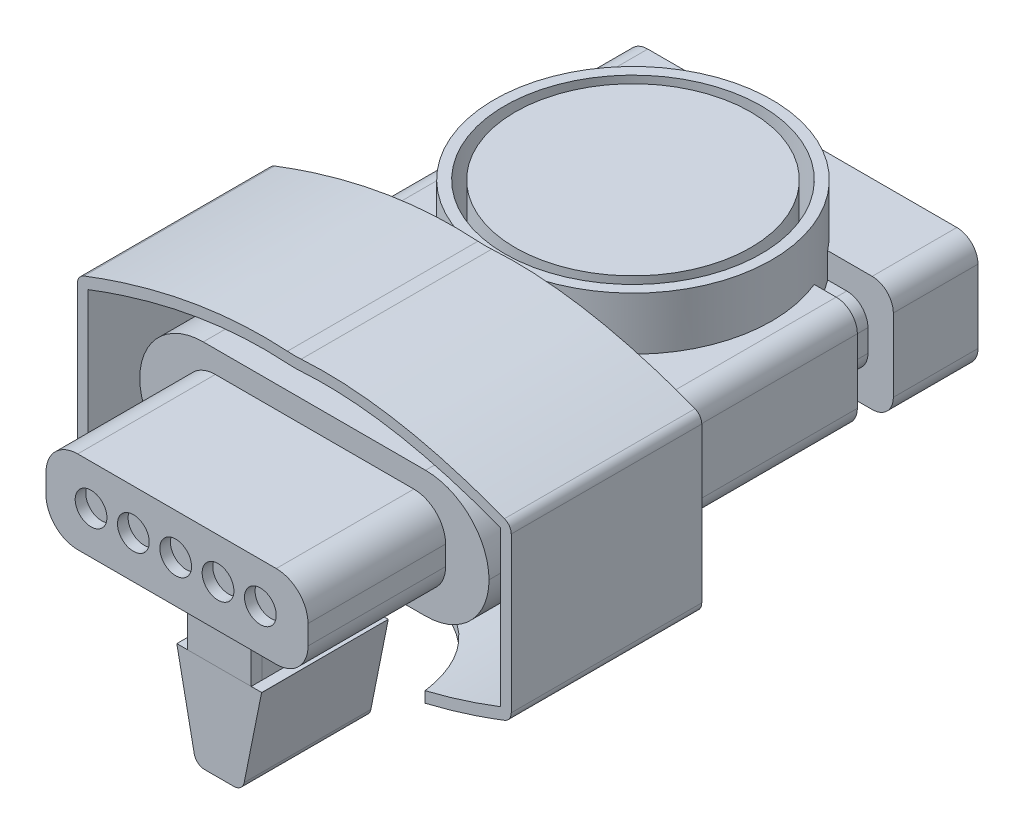
SolidWorks part; units mm, degrees
ref_plane "正面" through (0, 0, 0) normal (0, 0, 1) x (1, 0, 0)
ref_plane "平面" through (0, 0, 0) normal (0, 1, 0) x (1, 0, 0)
ref_plane "右側面" through (0, 0, 0) normal (1, 0, 0) x (0, 0, -1)
sketch "ｽｹｯﾁ1" plane through (0, 0, 0) normal (0, 0, 1) x (1, 0, 0)
  line L1 (0, 0) -> (33.2, 0)
  line L2 (0, 0) -> (0, 10.9)
  line L3 (0, 10.9) -> (33.2, 10.9)
  line L4 (33.2, 0) -> (33.2, 10.9)
  dimension "D1" = 10.9
  dimension "D2" = 33.2
extrude "ﾎﾞｽ - 押し出し1" add sketch "ｽｹｯﾁ1" along normal blind 8
sketch "ｽｹｯﾁ2" plane through (0, 0, 8) normal (0, 0, 1) x (1, 0, 0)
  line L8 (2.4, 8.5) -> (2.4, 2.4)
  line L9 (2.4, 2.4) -> (30.8, 2.4)
  line L10 (30.8, 2.4) -> (30.8, 8.5)
  line L11 (30.8, 8.5) -> (2.4, 8.5)
  line L12 (2.4, 8.5) -> (2.4, 2.4)
  line L13 (2.4, 2.4) -> (30.8, 2.4)
  line L14 (30.8, 2.4) -> (30.8, 8.5)
  line L15 (30.8, 8.5) -> (2.4, 8.5)
  dimension "D1" = 2.4
extrude "ﾎﾞｽ - 押し出し2" add sketch "ｽｹｯﾁ2" along normal blind 3
sketch "ｽｹｯﾁ3" plane through (0, 0, 11) normal (0, 0, 1) x (1, 0, 0)
  line L12 (32.8, 10.5) -> (0.4, 10.5)
  line L13 (0.4, 10.5) -> (0.4, 0.4)
  line L14 (0.4, 0.4) -> (32.8, 0.4)
  line L15 (32.8, 0.4) -> (32.8, 10.5)
  line L16 (32.8, 10.5) -> (0.4, 10.5)
  line L17 (0.4, 10.5) -> (0.4, 0.4)
  line L18 (0.4, 0.4) -> (32.8, 0.4)
  line L19 (32.8, 0.4) -> (32.8, 10.5)
  dimension "D1" = 2
extrude "ﾎﾞｽ - 押し出し3" add sketch "ｽｹｯﾁ3" along normal blind 19
sketch "ｽｹｯﾁ4" plane through (0, 0, 30) normal (0, 0, 1) x (1, 0, 0)
  line L1 (0.4, 10.5) -> (0.4, 0.4) construction
  line L2 (-3.9, -2.55) -> (-3.9, 13.45)
  line L3 (0.4, 5.45) -> (32.8, 5.45) construction
  line L4 (32.8, 0.4) -> (32.8, 10.5) construction
  line L5 (16.6, 10.5) -> (16.6, 0.4) construction
  line L6 (32.8, 10.5) -> (0.4, 10.5) construction
  line L7 (0.4, 0.4) -> (32.8, 0.4) construction
  line L8 (37.1, -2.55) -> (37.1, 13.45)
  line L9 (-3.9, 5.45) -> (-3.9, 13.45)
  spline S0 degree 3 poles (16.6, 17.1) (9.5929, 17.6967) (2.5741, 16.014) (-3.9, 13.45) knots 0 0 0 0 1 1 1 1
  spline S1 degree 3 poles (16.6, 17.1) (23.6071, 17.6967) (30.6259, 16.014) (37.1, 13.45) knots 0 0 0 0 1 1 1 1
  spline S2 degree 3 poles (16.6, -6.2) (23.6071, -6.7967) (30.6259, -5.114) (37.1, -2.55) knots 0 0 0 0 1 1 1 1
  spline S3 degree 3 poles (16.6, -6.2) (9.5929, -6.7967) (2.5741, -5.114) (-3.9, -2.55) knots 0 0 0 0 1 1 1 1
  point P22 (37.1, 5.45)
  dimension "D1" = 4.3
  dimension "D2" = 8
  dimension "D3" = 6.6
extrude "ﾎﾞｽ - 押し出し4" add sketch "ｽｹｯﾁ4" along normal blind 18 contours S0 S1 L8 S2 S3 L2
fillet "ﾌｨﾚｯﾄ1" radius 10 2 edges at (16.6, 17.1, 39) (16.6, -6.2, 39)
sketch "ｽｹｯﾁ5" plane through (0, 0, 48) normal (0, 0, 1) x (1, 0, 0)
  line L4 (-2.9, 12.7669) -> (-2.9, -1.8669)
  line L5 (36.1, -1.8669) -> (36.1, 12.7669)
  line L6 (-2.9, 12.7669) -> (-2.9, -1.8669)
  line L7 (36.1, -1.8669) -> (36.1, 12.7669)
  arc A4 (17.3158, -5.251) -> (15.8842, -5.251) centre (16.6, -16.2277) ccw
  arc A5 (15.8842, 16.151) -> (17.3158, 16.151) centre (16.6, 27.1277) ccw
  arc A6 (17.3158, -5.251) -> (15.8842, -5.251) centre (16.6, -16.2277) ccw
  arc A7 (15.8842, 16.151) -> (17.3158, 16.151) centre (16.6, 27.1277) ccw
  spline S8 degree 3 poles (-1595.7117, -3656.5086) (-104.425, 409.5804) (-109.7633, 29.6537) (3.1945, -3.8808) (4.7522, -4.2703) (7.1155, -4.729) (7.9088, -4.861) (9.4961, -5.0774) (10.291, -5.1621) (97.7123, -11.6496) (201.401, 283.2228) (496.6372, 3960.3055) knots -17.845867 -17.845867 -17.845867 -17.845867 0.25 0.25 0.5 0.5 0.625 0.625 0.75 0.75 14.346286 14.346286 14.346286 14.346286 only from (-2.9, -1.8669) to (15.8842, -5.251)
  spline S9 degree 3 poles (-303.7203, 3976.0592) (-161.6754, 304.9336) (-67.4702, -11.89) (22.9214, -5.161) (23.7203, -5.0755) (25.3086, -4.8583) (26.0992, -4.7264) (27.6736, -4.4203) (28.4581, -4.2459) (30.0141, -3.8604) (30.7864, -3.6491) (144.2827, 30.066) (147.6404, 421.65) (1528.8318, -3697.9846) knots -13.74633 -13.74633 -13.74633 -13.74633 0.25 0.25 0.375 0.375 0.5 0.5 0.625 0.625 0.75 0.75 19.116032 19.116032 19.116032 19.116032 only from (17.3158, -5.251) to (36.1, -1.8669)
  spline S10 degree 3 poles (1628.9117, 3667.4086) (137.625, -398.6804) (142.9633, -18.7537) (30.0055, 14.7808) (28.4478, 15.1703) (26.0845, 15.629) (25.2912, 15.761) (23.7039, 15.9774) (22.909, 16.0621) (-64.5123, 22.5496) (-168.201, -272.3228) (-463.4372, -3949.4055) knots -17.845867 -17.845867 -17.845867 -17.845867 0.25 0.25 0.5 0.5 0.625 0.625 0.75 0.75 14.346286 14.346286 14.346286 14.346286 only from (36.1, 12.7669) to (17.3158, 16.151)
  spline S11 degree 3 poles (336.9203, -3965.1592) (194.8754, -294.0336) (100.6702, 22.79) (10.2786, 16.061) (9.4797, 15.9755) (7.8914, 15.7583) (7.1008, 15.6264) (5.5264, 15.3203) (4.7419, 15.1459) (3.1859, 14.7604) (2.4136, 14.5491) (-111.0827, -19.166) (-114.4404, -410.75) (-1495.6318, 3708.8846) knots -13.74633 -13.74633 -13.74633 -13.74633 0.25 0.25 0.375 0.375 0.5 0.5 0.625 0.625 0.75 0.75 19.116032 19.116032 19.116032 19.116032 only from (15.8842, 16.151) to (-2.9, 12.7669)
  spline S12 degree 3 poles (-2.9, -1.8669) (-1.401, -2.4437) (0.116, -2.9668) (3.1945, -3.8808) (4.7522, -4.2703) (7.1155, -4.729) (7.9088, -4.861) (9.4961, -5.0774) (10.291, -5.1621) (12.6802, -5.3394) (14.2788, -5.3557) (15.8842, -5.251) knots 0 0 0 0 0.25 0.25 0.5 0.5 0.625 0.625 0.75 0.75 1 1 1 1
  spline S13 degree 3 poles (17.3158, -5.251) (18.9192, -5.3556) (20.521, -5.3397) (22.9214, -5.161) (23.7203, -5.0755) (25.3086, -4.8583) (26.0992, -4.7264) (27.6736, -4.4203) (28.4581, -4.2459) (30.0141, -3.8604) (30.7864, -3.6491) (33.0881, -2.9654) (34.6023, -2.4432) (36.1, -1.8669) knots 0 0 0 0 0.25 0.25 0.375 0.375 0.5 0.5 0.625 0.625 0.75 0.75 1 1 1 1
  spline S14 degree 3 poles (36.1, 12.7669) (34.601, 13.3437) (33.084, 13.8668) (30.0055, 14.7808) (28.4478, 15.1703) (26.0845, 15.629) (25.2912, 15.761) (23.7039, 15.9774) (22.909, 16.0621) (20.5198, 16.2394) (18.9212, 16.2557) (17.3158, 16.151) knots 0 0 0 0 0.25 0.25 0.5 0.5 0.625 0.625 0.75 0.75 1 1 1 1
  spline S15 degree 3 poles (15.8842, 16.151) (14.2808, 16.2556) (12.679, 16.2397) (10.2786, 16.061) (9.4797, 15.9755) (7.8914, 15.7583) (7.1008, 15.6264) (5.5264, 15.3203) (4.7419, 15.1459) (3.1859, 14.7604) (2.4136, 14.5491) (0.1119, 13.8654) (-1.4023, 13.3432) (-2.9, 12.7669) knots 0 0 0 0 0.25 0.25 0.375 0.375 0.5 0.5 0.625 0.625 0.75 0.75 1 1 1 1
  dimension "D1" = 1
extrude "ｶｯﾄ - 押し出し1" cut sketch "ｽｹｯﾁ5" against normal blind 15
sketch "ｽｹｯﾁ6" plane through (0, 0, 0) normal (0, 1, 0) x (1, 0, 0)
  line L0 (4.1448, -50.1641) -> (29.1448, -50.1641)
  arc A0 (29.1448, -50.1641) -> (4.1448, -50.1641) centre (16.6448, -50.1641) ccw
  dimension "D1" = 25
extrude "ｶｯﾄ - 押し出し2" cut sketch "ｽｹｯﾁ6" against normal blind 15
sketch "ｽｹｯﾁ7" plane through (0, 0, 33) normal (0, 0, 1) x (1, 0, 0)
  line L1 (0, 0) -> (33.0011, 0)
  line L2 (0, 0) -> (0, 11.9355)
  line L3 (0, 11.9355) -> (33.0011, 11.9355)
  line L4 (33.0011, 0) -> (33.0011, 11.9355)
extrude "ﾎﾞｽ - 押し出し5" add sketch "ｽｹｯﾁ7" along normal blind 13
fillet "ﾌｨﾚｯﾄ2" radius 6 4 edges at (0, 11.9355, 39.5) (0, 0, 39.5) (33.0011, 11.9355, 39.5) (33.0011, 0, 39.5)
sketch "ｽｹｯﾁ8" plane through (0, 0, 46) normal (0, 0, 1) x (1, 0, 0)
  line L1 (4.1401, 9.8417) -> (28.8957, 9.8417)
  line L2 (4.1401, 9.8417) -> (4.1401, 2.0004)
  line L3 (4.1401, 2.0004) -> (28.8957, 2.0004)
  line L4 (28.8957, 9.8417) -> (28.8957, 2.0004)
extrude "ﾎﾞｽ - 押し出し6" add sketch "ｽｹｯﾁ8" along normal blind 13
fillet "ﾌｨﾚｯﾄ3" radius 3 4 edges at (4.1401, 9.8417, 52.5) (4.1401, 2.0004, 52.5) (28.8957, 2.0004, 52.5) (28.8957, 9.8417, 52.5)
sketch "ｽｹｯﾁ9" plane through (0, 2.0004, 0) normal (0, -1, 0) x (1, 0, 0)
  line L0 (16.5005, 46) -> (12.5005, 46)
  line L1 (6, 46) -> (27.0011, 46) construction
  line L2 (16.5005, 46) -> (16.5179, 59) construction
  line L3 (7.1401, 59) -> (25.8957, 59) construction
  line L4 (12.5005, 46) -> (12.5005, 55)
  line L5 (12.5005, 55) -> (16.5126, 55)
  line L6 (16.5005, 46) -> (20.5005, 45.9893)
  line L7 (20.5005, 45.9893) -> (20.5246, 54.9893)
  line L8 (20.5246, 54.9893) -> (16.5126, 55)
  dimension "D1" = 4
  dimension "D2" = 9
extrude "ﾎﾞｽ - 押し出し7" add sketch "ｽｹｯﾁ9" along normal blind 2
sketch "ｽｹｯﾁ10" plane through (0, 0.0004, 0) normal (0, -1, 0) x (1, 0, 0)
  line L5 (13.5005, 54) -> (13.5005, 55)
  line L6 (16.5126, 55) -> (12.5005, 55) construction
  line L7 (13.5005, 55) -> (19.5219, 54.992)
  line L8 (20.5246, 54.9893) -> (16.5126, 55) construction
  line L9 (19.5219, 54.992) -> (19.5219, 53.992)
  line L10 (13.5005, 47) -> (19.5032, 47)
  line L11 (19.5032, 47) -> (19.5219, 53.992)
  line L12 (19.5219, 53.992) -> (16.5112, 54)
  line L13 (16.5112, 54) -> (13.5005, 54)
  line L14 (13.5005, 54) -> (13.5005, 47)
  line L15 (13.5005, 43.1087) -> (19.5032, 43.1087)
  line L16 (19.5032, 47) -> (19.5219, 53.992)
  line L17 (19.5032, 43.1087) -> (19.5032, 47)
  line L18 (13.5005, 47) -> (13.5005, 43.1087)
  line L19 (13.5005, 54) -> (13.5005, 47)
  dimension "D1" = 1
extrude "ﾎﾞｽ - 押し出し8" add sketch "ｽｹｯﾁ10" along normal blind 5
sketch "ｽｹｯﾁ11" plane through (0, -4.9996, 0) normal (0, -1, 0) x (1, 0, 0)
  line L0 (12.5005, 55) -> (20.5219, 54.9906)
  line L1 (12.5005, 43.024) -> (20.5032, 43.024)
  line L12 (20.5219, 55.9906) -> (12.5005, 56.0013)
  line L13 (12.5005, 56.0013) -> (12.5005, 42.1087)
  line L14 (12.5005, 42.1087) -> (20.5032, 42.1087)
  line L15 (20.5032, 42.1087) -> (20.5032, 46.9987)
  line L16 (20.5032, 46.9987) -> (20.5219, 53.9906)
  line L17 (20.5219, 53.9906) -> (20.5219, 55.9906)
  line L19 (12.5005, 55) -> (12.5005, 43.024)
  line L21 (20.5032, 43.024) -> (20.5032, 46.9987)
  line L22 (20.5032, 46.9987) -> (20.5219, 53.9906)
  line L23 (20.5219, 53.9906) -> (20.5219, 54.9906)
  dimension "D1" = 1
extrude "ﾎﾞｽ - 押し出し9" add sketch "ｽｹｯﾁ11" along normal blind 9
sketch "ｽｹｯﾁ12" plane through (0, 0, 43.024) normal (0, 0, -1) x (-1, 0, 0)
  line L0 (-18.698, -13.9996) -> (-20.5032, -4.9996)
  line L1 (-12.5005, -13.9996) -> (-20.5032, -13.9996) construction
  line L2 (-16.5019, -13.9996) -> (-16.5019, -4.9996) construction
  line L3 (-18.698, -13.9996) -> (-22.5672, -13.9996)
  line L4 (-22.5672, -13.9996) -> (-22.5672, -6.856)
  line L5 (-14.3058, -13.9996) -> (-12.5005, -13.9996)
  line L6 (-14.3058, -13.9996) -> (-12.5005, -4.9996)
  line L7 (-12.5005, -13.9996) -> (-12.5005, -4.9996)
  line L8 (-22.5672, -6.856) -> (-20.5032, -4.9996)
extrude "ｶｯﾄ - 押し出し7" cut sketch "ｽｹｯﾁ12" against normal blind 13
fillet "ﾌｨﾚｯﾄ4" radius 1 2 edges at (18.698, -13.9996, 49.0084) (14.3058, -13.9996, 49.0109)
fillet "ﾌｨﾚｯﾄ5" radius 1 4 edges at (37.1, -2.55, 39) (37.1, 13.45, 39) (-3.9, 13.45, 39) (-3.9, -2.55, 39)
fillet "ﾌｨﾚｯﾄ6" radius 2 12 edges at (0, 0, 4) (2.4, 2.4, 9.5) (0.4, 0.4, 20.5) (2.4, 8.5, 9.5) (0, 10.9, 4) (0.4, 10.5, 20.5) (30.8, 8.5, 9.5) (33.2, 10.9, 4) (32.8, 10.5, 20.5) (33.2, 0, 4) (30.8, 2.4, 9.5) (32.8, 0.4, 20.5)
sketch "ｽｹｯﾁ14" plane through (0, 8.5, 0) normal (0, 1, 0) x (1, 0, 0)
  line L0 (16.6, -30) -> (16.6, -16) construction
  line L1 (30.8, -30) -> (2.4, -30) construction
  circle A0 centre (16.6, -16) radius 13.1177
  dimension "D1" = 14
extrude "ﾎﾞｽ - 押し出し15" add sketch "ｽｹｯﾁ14" along normal blind 7
sketch "ｽｹｯﾁ15" plane through (0, 15.5, 0) normal (0, 1, 0) x (1, 0, 0)
  circle A1 centre (16.6, -16) radius 11.1177
  circle A2 centre (16.6, -16) radius 12.1177
  circle A3 centre (16.6, -16) radius 12.1177
  dimension "D1" = 1
  dimension "D2" = 1
extrude "ｶｯﾄ - 押し出し8" cut sketch "ｽｹｯﾁ15" against normal blind 7
sketch "ｽｹｯﾁ16" plane through (0, 0, 0) normal (0, 0, -1) x (-1, 0, 0)
  line L0 (-6.6, 6) -> (-26.6, 6) construction
  line L1 (-2, 0) -> (-31.2, 0) construction
  line L2 (0, 8.9) -> (0, 2) construction
  circle A0 centre (-16.6, 6) radius 2
  circle A1 centre (-11.6, 6) radius 2
  circle A2 centre (-21.6, 6) radius 2
  circle A3 centre (-26.6, 6) radius 2
  circle A4 centre (-6.6, 6) radius 2
  dimension "D1" = 4
  dimension "D2" = 6
  dimension "D3" = 16.6
  dimension "D4" = 5
  dimension "D5" = 5
  dimension "D6" = 5
  dimension "D7" = 5
extrude "ｶｯﾄ - 押し出し9" cut sketch "ｽｹｯﾁ16" against normal blind 1
sketch "ｽｹｯﾁ17" plane through (0, 0, 59) normal (0, 0, 1) x (1, 0, 0)
  line L0 (28.8957, 5.0004) -> (28.8957, 6.8417) construction
  line L1 (7.1401, 2.0004) -> (25.8957, 2.0004) construction
  circle A0 centre (16.3957, 6.0004) radius 1.5
  circle A1 centre (20.3957, 6.0004) radius 1.5
  circle A2 centre (24.3957, 6.0004) radius 1.5
  circle A3 centre (12.3957, 6.0004) radius 1.5
  circle A4 centre (8.3957, 6.0004) radius 1.5
  dimension "D1" = 3
  dimension "D5" = 8
  dimension "D2" = 12.5
  dimension "D3" = 4
  dimension "D7" = 8
  dimension "D4" = 3
  dimension "D6" = 3
extrude "ｶｯﾄ - 押し出し10" cut sketch "ｽｹｯﾁ17" against normal blind 1
